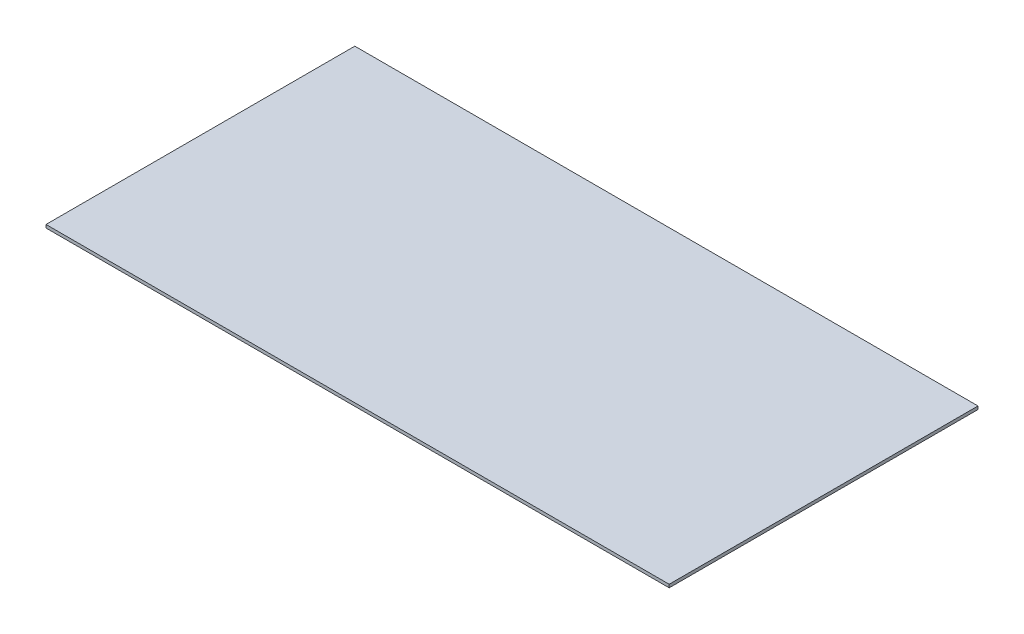
SolidWorks part; units mm, degrees
material "6061-T6 (SS)"
ref_plane "X-Y Datum" through (0, 0, 0) normal (0, 0, 1) x (1, 0, 0)
ref_plane "X-Z Datum" through (0, 0, 0) normal (0, 1, 0) x (1, 0, 0)
ref_plane "Y-Z Datum" through (0, 0, 0) normal (1, 0, 0) x (0, 0, -1)
sketch "Sketch1" plane through (0, 0, 0) normal (0, 0, 1) x (1, 0, 0)
  line L1 (-228.6, -1.143) -> (228.6, -1.143)
  line L2 (-228.6, -1.143) -> (-228.6, 1.143)
  line L3 (-228.6, 1.143) -> (228.6, 1.143)
  line L4 (228.6, -1.143) -> (228.6, 1.143)
  line L5 (-228.6, -1.143) -> (228.6, 1.143) construction
  line L6 (-228.6, 1.143) -> (228.6, -1.143) construction
  point P0 (0, 0)
  dimension "D1" = 2.286
  dimension "D2" = 457.2
extrude "Boss-Extrude1" add sketch "Sketch1" along normal blind 223.38
sketch "Sketch2" plane through (0, 0, 0) normal (0, 0, -1) x (-1, 0, 0)
  line L22 (-228.6, 1.143) -> (-228.6, -1.143)
  line L23 (-228.6, -1.143) -> (228.6, -1.143)
  line L24 (228.6, -1.143) -> (228.6, 1.143)
  line L25 (228.6, 1.143) -> (-228.6, 1.143)
  line L26 (-228.6, 1.143) -> (-228.6, -1.143)
  line L27 (-228.6, -1.143) -> (228.6, -1.143)
  line L28 (228.6, -1.143) -> (228.6, 1.143)
  line L29 (228.6, 1.143) -> (-228.6, 1.143)
  line M6 (-228.6, -1.143) -> (228.6, -1.143)
  line M8 (228.6, 1.143) -> (-228.6, 1.143)
  dimension "D1" = 0
extrude "Boss-Extrude2" add sketch "Sketch2" along normal blind 3.175 contours M8 M6 | M8 M6 region at (0, 0, 0)
